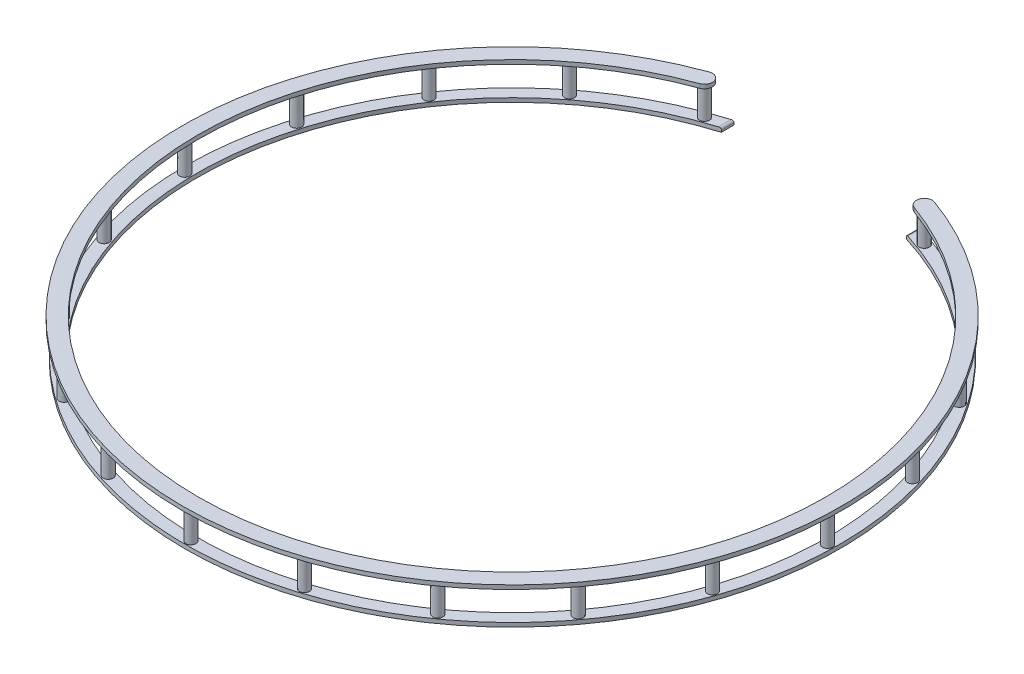
SolidWorks part; units mm, degrees
material "Alloy Steel"
ref_plane "Front Plane" through (0, 0, 0) normal (0, 0, 1) x (1, 0, 0)
ref_plane "Top Plane" through (0, 0, 0) normal (0, 1, 0) x (1, 0, 0)
ref_plane "Right Plane" through (0, 0, 0) normal (1, 0, 0) x (0, 0, -1)
sketch "Sketch1" plane through (0, 0, 0) normal (0, 1, 0) x (1, 0, 0)
  circle A0 centre (0, 0) radius 7830.5409
  circle A1 centre (0, 0) radius 8130.5409
  dimension "D1" = 15661.0818
  dimension "D2" = 300
extrude "Boss-Extrude1" add sketch "Sketch1" along normal blind 100
sketch "Sketch2" plane through (0, 100, 0) normal (0, 1, 0) x (1, 0, 0)
  line L1 (-1850, 8833.8276) -> (1850, 8833.8276)
  line L2 (-1850, 8833.8276) -> (-1850, 6827.2542)
  line L3 (-1850, 6827.2542) -> (1850, 6827.2542)
  line L4 (1850, 8833.8276) -> (1850, 6827.2542)
  line L5 (-1850, 8833.8276) -> (1850, 6827.2542) construction
  line L6 (-1850, 6827.2542) -> (1850, 8833.8276) construction
  circle A0 centre (0, 0) radius 7830.5409 construction
  point P0 (0, 7830.5409)
  dimension "D1" = 3700
extrude "Cut-Extrude1" cut sketch "Sketch2" against normal blind 100 and the other way blind 100
sketch "Sketch4" plane through (0, 100, 0) normal (0, 1, 0) x (1, 0, 0)
  line L0 (0, -7830.5409) -> (0, -8130.5409) construction
  arc A0 (-1850, 7608.8679) -> (1850, 7608.8679) centre (0, 0) ccw construction
  arc A1 (-1850, 7917.272) -> (1850, 7917.272) centre (0, 0) ccw construction
  circle A2 centre (0, -7980.5409) radius 125
  dimension "D1" = 250
extrude "Boss-Extrude2" add sketch "Sketch4" along normal blind 750
pattern_circular "CirPattern1" count 10 every 17.778 about axis through (0, 100, 0) along (0, 1, 0) of "Boss-Extrude2" other way count 10
ref_plane "Plane2" through (0, 850, 0) normal (0, 1, 0) x (1, 0, 0)
sketch "Sketch5" plane through (0, 850, 0) normal (0, 1, 0) x (1, 0, 0)
  arc A0 (-2729.5057, 7499.2554) -> (2729.5057, 7499.2554) centre (0, -7.4092) ccw construction
  arc A1 (-2796.4047, 7683.2403) -> (2796.4047, 7683.2403) centre (0, -7.4092) ccw
  arc A2 (-2662.6068, 7315.2705) -> (2662.6068, 7315.2705) centre (0, -7.4092) ccw
  arc A3 (-2662.6068, 7315.2705) -> (-2796.4047, 7683.2403) centre (-2729.5057, 7499.2554) ccw
  arc A4 (2796.4047, 7683.2403) -> (2662.6068, 7315.2705) centre (2729.5057, 7499.2554) ccw
  point P3 (0, -7994.9128)
extrude "Boss-Extrude3" add sketch "Sketch5" along normal blind 100
sketch "Sketch6" plane through (0, 100, 0) normal (0, 1, 0) x (1, 0, 0)
  line L1 (-2296.3939, 8137.3759) -> (2296.3939, 8137.3759)
  line L2 (-2296.3939, 8137.3759) -> (-2296.3939, 7404.2483)
  line L3 (-2296.3939, 7404.2483) -> (2296.3939, 7404.2483)
  line L4 (2296.3939, 8137.3759) -> (2296.3939, 7404.2483)
  line L5 (-2296.3939, 8137.3759) -> (2296.3939, 7404.2483) construction
  line L6 (-2296.3939, 7404.2483) -> (2296.3939, 8137.3759) construction
  point P0 (0, 7770.8121)
extrude "Cut-Extrude2" cut sketch "Sketch6" against normal blind 2000 and the other way blind 2000
fillet "Fillet1" radius 50 1 edges at (-2296.3939, 100, -7642.8775)
fillet "Fillet2" radius 50 1 edges at (2296.3939, 100, -7642.8775)
